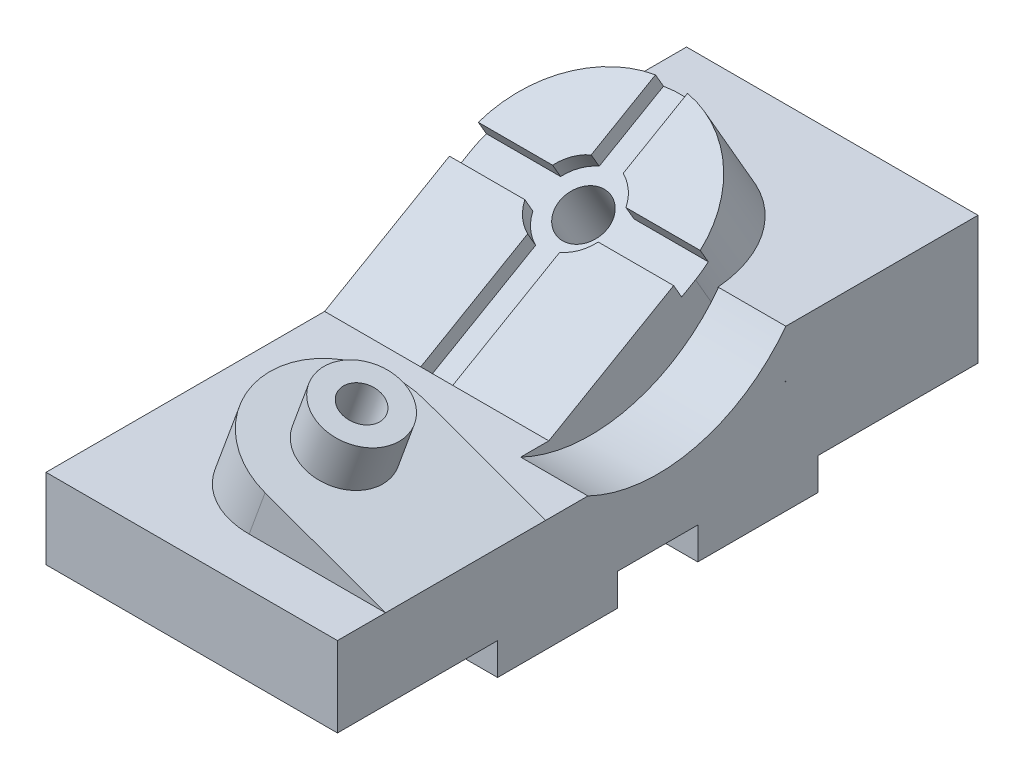
SolidWorks part; units mm, degrees
note: The reader was unsure of these and kept them because the rebuilt part matched: shared geometry of "Sketch1<3>", "Sketch4<4>", "Sketch4<5>", "Sketch6<2>", "Sketch9<5>", "Sketch9<6>", "Sketch9<7>".
ref_plane "Front Plane" through (0, 0, 0) normal (0, 0, 1) x (1, 0, 0)
ref_plane "Top Plane" through (0, 0, 0) normal (0, 1, 0) x (1, 0, 0)
ref_plane "Right Plane" through (0, 0, 0) normal (1, 0, 0) x (0, 0, -1)
sketch "Sketch1" plane through (0, 0, 0) normal (0, 1, 0) x (0, 0, -1)
  line L0 (50, 91) -> (50, 0)
  line L1 (0, 0) -> (200, 0)
  line L2 (0, 0) -> (0, 91)
  line L3 (0, 91) -> (200, 91)
  line L4 (200, 0) -> (200, 91)
  line L5 (87.5, 91) -> (87.5, 0)
  line L6 (112.5, 91) -> (112.5, 0)
  line L7 (150, 91) -> (150, 0)
  dimension "D1" = 200
  dimension "D2" = 91
  dimension "D3" = 50
  dimension "D4" = 37.5
  dimension "D5" = 25
  dimension "D6" = 100
extrude "Boss-Extrude1" add sketch "Sketch1" against normal blind 25 contours L3 L2 L1 L0 | L5 L3 L0 L1 | L6 L3 L5 L1 | L7 L3 L6 L1 | L3 L7 L1 L4
extrude "Boss-Extrude2" add sketch "Sketch1<3>" against normal blind 35 contours L5 L3 L0 L1 | L7 L3 L6 L1
sketch "Sketch1<3>" plane through (0, 0, 0) normal (0, 1, 0) x (0, 0, -1) same geometry as "Sketch1"
sketch "Sketch3" plane through (0, 0, 0) normal (0, 0, 1) x (1, 0, 0)
  line L0 (-53.0308, 19.3016) -> (0, 0) construction
  line L2 (0, 0) -> (-91, 0) construction
  point P0 (-53.0308, 19.3016)
  dimension "D1" = 20
ref_plane "Plane1" through (0, 0, 0) normal (0.342, 0.9397, 0) x (0.9397, -0.342, 0)
sketch "Sketch4" plane through (0, 0, 0) normal (0.342, 0.9397, 0) x (0.9397, -0.342, 0)
  line L0 (0, 15) -> (-40, 15)
  line L1 (0, 0) -> (0, 200) construction
  line L2 (-40, 65) -> (0, 65)
  line L3 (0, 0) -> (-85.512, 0) construction
  line L5 (0, 15) -> (0, 65)
  arc A0 (-40, 15) -> (-40, 65) centre (-40, 40) cw
  circle A1 centre (-40, 40) radius 6
  circle A2 centre (-40, 40) radius 12.5
  dimension "D1" = 25
  dimension "D4" = 12
  dimension "D5" = 25
  dimension "D2" = 40
  dimension "D3" = 15
extrude "Boss-Extrude3" add sketch "Sketch4" against normal up to surface (14.5588 mm away) contours A0 L0 L5 L2 A2 | A2 A1
extrude "Cut-Extrude1" cut sketch "Sketch4<4>" against normal through all contours A1
sketch "Sketch4<4>" plane through (0, 0, 0) normal (0.342, 0.9397, 0) x (0.9397, -0.342, 0) same geometry as "Sketch4"
extrude "Boss-Extrude4" add sketch "Sketch4<5>" along normal blind 15 contours A2 A1
sketch "Sketch4<5>" plane through (0, 0, 0) normal (0.342, 0.9397, 0) x (0.9397, -0.342, 0) same geometry as "Sketch4"
sketch "Sketch5" plane through (0, 0, 0) normal (0, 1, 0) x (1, 0, 0)
  line L0 (-91, 140) -> (0, 140)
  line L1 (-91, 0) -> (-91, 200) construction
  line L2 (0, 65) -> (0, 200) construction
  line L3 (0, 200) -> (-91, 200) construction
  line L4 (0, 140) -> (0, 200)
  line L5 (0, 200) -> (-91, 200)
  line L6 (-91, 200) -> (-91, 140)
  dimension "D1" = 60
extrude "Boss-Extrude5" add sketch "Sketch5" along normal blind 15
sketch "Sketch6" plane through (0, 0, 0) normal (1, 0, 0) x (0, 0, -1)
  line L0 (140, 15) -> (200, 15) construction
  line L1 (140, 15) -> (200, 15)
  line L2 (200, -25) -> (200, 15) construction
  line L4 (100, -5) -> (55.9075, -5) construction
  line L5 (65, 0) -> (140, 0) construction
  arc A0 (78.2055, 0) -> (140, 15) centre (100, 45) ccw
  point P9 (0, 0)
  point P12 (0, 0)
  dimension "D1" = 50
  dimension "D2" = 60
  dimension "D3" = 5
extrude "Cut-Extrude2" cut sketch "Sketch6" against normal blind 21 and the other way through all
sketch "Sketch7" plane through (0, 0, 0) normal (0, 1, 0) x (1, 0, 0)
  line L0 (-91, 87) -> (-21, 87)
  line L1 (-91, 0) -> (-91, 140) construction
  line L2 (-21, 78.2055) -> (-21, 121.7945) construction
  line L3 (0, 0) -> (-91, 0) construction
  dimension "D1" = 87
extrude "Extrude-Thin1" add sketch "Sketch6<2>" against normal blind 21 thin
sketch "Sketch6<2>" plane through (0, 0, 0) normal (1, 0, 0) x (0, 0, -1) same geometry as "Sketch6"
sketch "Sketch8" plane through (-91, 0, 0) normal (-1, 0, 0) x (0, 0, 1)
  line L0 (-87, 0) -> (-130.3013, 25) construction
  line L1 (0, 0) -> (-140, 0) construction
  dimension "D1" = 50
  dimension "D2" = 30
ref_plane "Plane3" through (0, -37.6721, -21.75) normal (0, 0.866, 0.5) x (1, 0, 0)
sketch "Sketch9" plane through (0, -37.6721, -21.75) normal (0, 0.866, 0.5) x (1, 0, 0)
  line L0 (-21, 75.3442) -> (-21, 125.3442)
  line L1 (-91, 75.3442) -> (-21, 75.3442) construction
  line L2 (-91, 75.3442) -> (-21, 75.3442)
  line L3 (-91, 75.3442) -> (-91, 125.3442)
  line L4 (-91, 125.3442) -> (-68.5, 125.3442) construction
  line L5 (-61, 75.3442) -> (-61, 113.8878)
  line L6 (-51, 159.9852) -> (-51, 136.8006)
  line L7 (-21.359, 130.3442) -> (-44.5436, 130.3442)
  line L8 (-91, 120.3442) -> (-67.4564, 120.3442)
  line L9 (-56, 160.3442) -> (-56, 137.8442) construction
  line L10 (-43.5, 125.3442) -> (-21, 125.3442) construction
  line L11 (-51, 113.8878) -> (-51, 75.3442)
  line L12 (-56, 112.8442) -> (-56, 75.3442) construction
  line L13 (-61, 136.8006) -> (-61, 159.9852)
  line L14 (-44.5436, 120.3442) -> (-21, 120.3442)
  line L15 (-67.4564, 130.3442) -> (-90.641, 130.3442)
  arc A0 (-91, 125.3442) -> (-21, 125.3442) centre (-56, 125.3442) cw
  circle A1 centre (-56, 125.3442) radius 7.5
  circle A2 centre (-56, 125.3442) radius 12.5
  dimension "D2" = 10
  dimension "D4" = 15
  dimension "D5" = 25
  dimension "D1" = 10
  dimension "D3" = 50
extrude "Boss-Extrude6" add sketch "Sketch9" against normal up to next
extrude "Cut-Extrude4" cut sketch "Sketch9<5>" against normal blind 5 contours A1 L6 A0 L13 | A1 L14 L0 A0 L7 | A1 L5 L2 L11 | A1 L15 A0 L3 L8
sketch "Sketch9<5>" plane through (0, -37.6721, -21.75) normal (0, 0.866, 0.5) x (1, 0, 0) same geometry as "Sketch9"
extrude "Cut-Extrude5" cut sketch "Sketch9<6>" against normal blind 5 contours A2 A1
sketch "Sketch9<6>" plane through (0, -37.6721, -21.75) normal (0, 0.866, 0.5) x (1, 0, 0) same geometry as "Sketch9"
extrude "Cut-Extrude6" cut sketch "Sketch9<7>" against normal through all contours A1
sketch "Sketch9<7>" plane through (0, -37.6721, -21.75) normal (0, 0.866, 0.5) x (1, 0, 0) same geometry as "Sketch9"
equation "\"A\"=91"
equation "\"D2@Sketch1\"=\"A\""
equation "\"D1@Cut-Extrude2\"=\"A\"-70"
